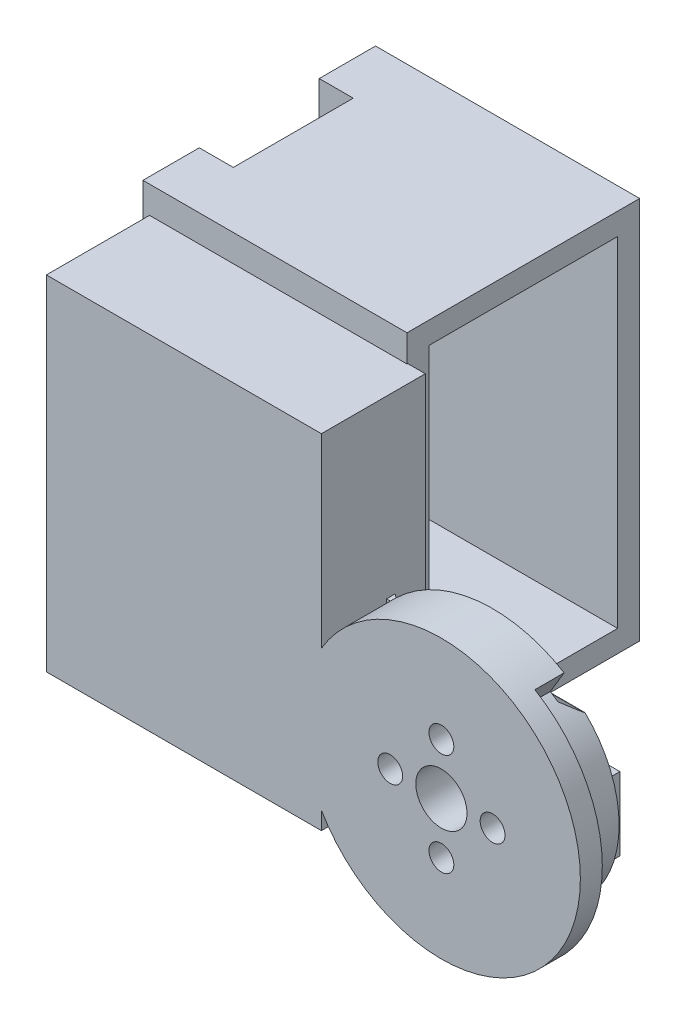
SolidWorks part; units mm, degrees
ref_plane "Front Plane" through (0, 0, 0) normal (0, 0, 1) x (1, 0, 0)
ref_plane "Top Plane" through (0, 0, 0) normal (0, 1, 0) x (1, 0, 0)
ref_plane "Right Plane" through (0, 0, 0) normal (1, 0, 0) x (0, 0, -1)
ref_plane "PZ_p23_000" through (0, 0, 23) normal (0, 0, 1) x (1, 0, 0)
sketch "S_cyl1" plane through (0, 0, 23) normal (0, 0, 1) x (1, 0, 0)
  circle A0 centre (0, 0) radius 19
  dimension "D1_S_cyl1" = 38
extrude "Boss_1" add sketch "S_cyl1" along normal blind 7
ref_plane "PZ_p21_000" through (0, 0, 21) normal (0, 0, 1) x (1, 0, 0)
sketch "S_prism2" plane through (0, 0, 21) normal (0, 0, 1) x (1, 0, 0)
  line L0 (-15.4919, 11) -> (15.4919, 11)
  line L1 (15.4919, -11) -> (-15.4919, -11)
  arc A0 (15.4919, 11) -> (15.4919, -11) centre (0, 0) cw
  arc A1 (-15.4919, -11) -> (-15.4919, 11) centre (0, 0) cw
extrude "Boss_2" add sketch "S_prism2" along normal blind 2.1
ref_plane "PZ_p19_600" through (0, 0, 19.6) normal (0, 0, 1) x (1, 0, 0)
sketch "S_box3" plane through (0, 0, 19.6) normal (0, 0, 1) x (1, 0, 0)
  line L0 (-14.2, -5) -> (14, -5)
  line L1 (14, -5) -> (14, 5)
  line L2 (14, 5) -> (-14.2, 5)
  line L3 (-14.2, 5) -> (-14.2, -5)
  dimension "P1" = 14.2
  dimension "P2" = 5
  dimension "P3" = 14
  dimension "P4" = 5
  dimension "P5" = 14
  dimension "P6" = 5
  dimension "P7" = 14.2
  dimension "P8" = 5
extrude "Boss_3" add sketch "S_box3" along normal blind 1.5
ref_plane "PZ_p15_800" through (0, 0, 15.8) normal (0, 0, 1) x (1, 0, 0)
sketch "S_box4" plane through (0, 0, 15.8) normal (0, 0, 1) x (1, 0, 0)
  line L0 (-54, -12) -> (-16.4, -12)
  line L1 (-16.4, -12) -> (-16.4, 35)
  line L2 (-16.4, 35) -> (-54, 35)
  line L3 (-54, 35) -> (-54, -12)
  dimension "P1" = 54
  dimension "P2" = 12
  dimension "P3" = 16.4
  dimension "P4" = 12
  dimension "P5" = 16.4
  dimension "P6" = 35
  dimension "P7" = 54
  dimension "P8" = 35
extrude "Boss_4" add sketch "S_box4" along normal blind 14.2
ref_plane "PX_m11_500" through (-11.5, 0, 0) normal (1, 0, 0) x (0, 0, -1)
sketch "S_prism5" plane through (-11.5, 0, 0) normal (1, 0, 0) x (0, 0, -1)
  line L0 (-21.05, 11) -> (-21.05, -12)
  line L1 (-21.05, -12) -> (-23.1, -15)
  line L2 (-23.1, -15) -> (-23.1, 12.5)
  line L3 (-23.1, 12.5) -> (-21.05, 11)
extrude "Boss_5" add sketch "S_prism5" along normal blind 23
ref_plane "PY_m11_000" through (0, -11, 0) normal (0, 1, 0) x (1, 0, 0)
sketch "S_prism6" plane through (0, -11, 0) normal (0, 1, 0) x (1, 0, 0)
  line L0 (-16.45, -21.1) -> (-16.45, -19.9)
  line L1 (-16.45, -19.9) -> (-14.8, -21.1)
  line L2 (-14.8, -21.1) -> (-16.45, -21.1)
extrude "Boss_6" add sketch "S_prism6" along normal blind 22
ref_plane "PZ_m15_900" through (0, 0, -15.9) normal (0, 0, 1) x (1, 0, 0)
sketch "S_box7" plane through (0, 0, -15.9) normal (0, 0, 1) x (1, 0, 0)
  line L0 (-54.9, 35.7) -> (-18.8, 35.7)
  line L1 (-18.8, 35.7) -> (-18.8, 38.7)
  line L2 (-18.8, 38.7) -> (-54.9, 38.7)
  line L3 (-54.9, 38.7) -> (-54.9, 35.7)
  dimension "P1" = 54.9
  dimension "P2" = 35.7
  dimension "P3" = 18.8
  dimension "P4" = 35.7
  dimension "P5" = 18.8
  dimension "P6" = 38.7
  dimension "P7" = 54.9
  dimension "P8" = 38.7
extrude "Boss_7" add sketch "S_box7" along normal blind 31.8
sketch "S_box8" plane through (0, 0, -15.9) normal (0, 0, 1) x (1, 0, 0)
  line L0 (-54.9, -13.7) -> (-18.8, -13.7)
  line L1 (-18.8, -13.7) -> (-18.8, -10.7)
  line L2 (-18.8, -10.7) -> (-54.9, -10.7)
  line L3 (-54.9, -10.7) -> (-54.9, -13.7)
  dimension "P1" = 54.9
  dimension "P2" = 13.7
  dimension "P3" = 18.8
  dimension "P4" = 13.7
  dimension "P5" = 18.8
  dimension "P6" = 10.7
  dimension "P7" = 54.9
  dimension "P8" = 10.7
extrude "Boss_8" add sketch "S_box8" along normal blind 31.8
sketch "S_box9" plane through (0, 0, -15.9) normal (0, 0, 1) x (1, 0, 0)
  line L0 (-54.9, -13.7) -> (-18.8, -13.7)
  line L1 (-18.8, -13.7) -> (-18.8, 38.7)
  line L2 (-18.8, 38.7) -> (-54.9, 38.7)
  line L3 (-54.9, 38.7) -> (-54.9, -13.7)
  dimension "P1" = 54.9
  dimension "P2" = 13.7
  dimension "P3" = 18.8
  dimension "P4" = 13.7
  dimension "P5" = 18.8
  dimension "P6" = 38.7
  dimension "P7" = 54.9
  dimension "P8" = 38.7
extrude "Boss_9" add sketch "S_box9" along normal blind 3
ref_plane "PZ_p12_900" through (0, 0, 12.9) normal (0, 0, 1) x (1, 0, 0)
sketch "S_box10" plane through (0, 0, 12.9) normal (0, 0, 1) x (1, 0, 0)
  line L0 (-54.9, -13.7) -> (-18.8, -13.7)
  line L1 (-18.8, -13.7) -> (-18.8, 38.7)
  line L2 (-18.8, 38.7) -> (-54.9, 38.7)
  line L3 (-54.9, 38.7) -> (-54.9, -13.7)
  dimension "P1" = 54.9
  dimension "P2" = 13.7
  dimension "P3" = 18.8
  dimension "P4" = 13.7
  dimension "P5" = 18.8
  dimension "P6" = 38.7
  dimension "P7" = 54.9
  dimension "P8" = 38.7
extrude "Boss_10" add sketch "S_box10" along normal blind 3
sketch "S_box11" plane through (0, 0, -15.9) normal (0, 0, 1) x (1, 0, 0)
  line L0 (-54.9, -13.7) -> (-50.3, -13.7)
  line L1 (-50.3, -13.7) -> (-50.3, 38.7)
  line L2 (-50.3, 38.7) -> (-54.9, 38.7)
  line L3 (-54.9, 38.7) -> (-54.9, -13.7)
  dimension "P1" = 54.9
  dimension "P2" = 13.7
  dimension "P3" = 50.3
  dimension "P4" = 13.7
  dimension "P5" = 50.3
  dimension "P6" = 38.7
  dimension "P7" = 54.9
  dimension "P8" = 38.7
extrude "Boss_11" add sketch "S_box11" along normal blind 31.8
ref_plane "PX_m55_000" through (-55, 0, 0) normal (1, 0, 0) x (0, 0, -1)
sketch "S_hole12" plane through (-55, 0, 0) normal (1, 0, 0) x (0, 0, -1)
  circle A0 centre (0, 0) radius 10.5
  dimension "D1_S_hole12" = 21
extrude "Hole_12" cut sketch "S_hole12" along normal blind 4.8
ref_plane "PZ_m9_700" through (0, 0, -9.7) normal (0, 0, 1) x (1, 0, 0)
sketch "S_cut13" plane through (0, 0, -9.7) normal (0, 0, 1) x (1, 0, 0)
  line L0 (-55, 10.9) -> (-50.25, 10.9)
  line L1 (-50.25, 10.9) -> (-50.25, 30.4)
  line L2 (-50.25, 30.4) -> (-55, 30.4)
  line L3 (-55, 30.4) -> (-55, 10.9)
  dimension "P1" = 55
  dimension "P2" = 10.9
  dimension "P3" = 50.25
  dimension "P4" = 10.9
  dimension "P5" = 50.25
  dimension "P6" = 30.4
  dimension "P7" = 55
  dimension "P8" = 30.4
extrude "Pocket_13" cut sketch "S_cut13" along normal blind 19.4
ref_plane "PZ_m8_200" through (0, 0, -8.2) normal (0, 0, 1) x (1, 0, 0)
sketch "S_cut14" plane through (0, 0, -8.2) normal (0, 0, 1) x (1, 0, 0)
  line L0 (-55, 30.4) -> (-50.25, 30.4)
  line L1 (-50.25, 30.4) -> (-50.25, 39.2)
  line L2 (-50.25, 39.2) -> (-55, 39.2)
  line L3 (-55, 39.2) -> (-55, 30.4)
  dimension "P1" = 55
  dimension "P2" = 30.4
  dimension "P3" = 50.25
  dimension "P4" = 30.4
  dimension "P5" = 50.25
  dimension "P6" = 39.2
  dimension "P7" = 55
  dimension "P8" = 39.2
extrude "Pocket_14" cut sketch "S_cut14" along normal blind 16.4
ref_plane "PZ_m3_500" through (0, 0, -3.5) normal (0, 0, 1) x (1, 0, 0)
sketch "S_cut15" plane through (0, 0, -3.5) normal (0, 0, 1) x (1, 0, 0)
  line L0 (-55, 0) -> (-50.25, 0)
  line L1 (-50.25, 0) -> (-50.25, 11)
  line L2 (-50.25, 11) -> (-55, 11)
  line L3 (-55, 11) -> (-55, 0)
  dimension "P1" = 55
  dimension "P2" = 50.25
  dimension "P3" = 50.25
  dimension "P4" = 11
  dimension "P5" = 55
  dimension "P6" = 11
extrude "Pocket_15" cut sketch "S_cut15" along normal blind 7
ref_plane "PZ_m16_400" through (0, 0, -16.4) normal (0, 0, 1) x (1, 0, 0)
sketch "S_cut16" plane through (0, 0, -16.4) normal (0, 0, 1) x (1, 0, 0)
  line L0 (-55.1, -10) -> (-52.2, -10)
  line L1 (-52.2, -10) -> (-52.2, 10)
  line L2 (-52.2, 10) -> (-55.1, 10)
  line L3 (-55.1, 10) -> (-55.1, -10)
  dimension "P1" = 55.1
  dimension "P2" = 10
  dimension "P3" = 52.2
  dimension "P4" = 10
  dimension "P5" = 52.2
  dimension "P6" = 10
  dimension "P7" = 55.1
  dimension "P8" = 10
extrude "Pocket_16" cut sketch "S_cut16" along normal blind 16.4
sketch "S_hole17" plane through (-55, 0, 0) normal (1, 0, 0) x (0, 0, -1)
  circle A0 centre (-10.25, 8.3) radius 1.1
  dimension "D1_S_hole17" = 2.2
  dimension "P2" = 10.25
  dimension "P3" = 8.3
extrude "Hole_17" cut sketch "S_hole17" along normal blind 4.8
sketch "S_hole18" plane through (-55, 0, 0) normal (1, 0, 0) x (0, 0, -1)
  circle A0 centre (-10.25, 8.3) radius 2.3
  dimension "D1_S_hole18" = 4.6
  dimension "P2" = 10.25
  dimension "P3" = 8.3
extrude "Hole_18" cut sketch "S_hole18" along normal blind 1.7
sketch "S_hole19" plane through (-55, 0, 0) normal (1, 0, 0) x (0, 0, -1)
  circle A0 centre (10.25, 32.75) radius 1.1
  dimension "D1_S_hole19" = 2.2
  dimension "P2" = 10.25
  dimension "P3" = 32.75
extrude "Hole_19" cut sketch "S_hole19" along normal blind 4.8
sketch "S_hole20" plane through (-55, 0, 0) normal (1, 0, 0) x (0, 0, -1)
  circle A0 centre (10.25, 32.75) radius 2.3
  dimension "D1_S_hole20" = 4.6
  dimension "P2" = 10.25
  dimension "P3" = 32.75
extrude "Hole_20" cut sketch "S_hole20" along normal blind 1.7
sketch "S_hole21" plane through (-55, 0, 0) normal (1, 0, 0) x (0, 0, -1)
  circle A0 centre (-10.25, 32.75) radius 1.1
  dimension "D1_S_hole21" = 2.2
  dimension "P2" = 10.25
  dimension "P3" = 32.75
extrude "Hole_21" cut sketch "S_hole21" along normal blind 4.8
sketch "S_hole22" plane through (-55, 0, 0) normal (1, 0, 0) x (0, 0, -1)
  circle A0 centre (-10.25, 32.75) radius 2.3
  dimension "D1_S_hole22" = 4.6
  dimension "P2" = 10.25
  dimension "P3" = 32.75
extrude "Hole_22" cut sketch "S_hole22" along normal blind 1.7
ref_plane "PZ_p20_900" through (0, 0, 20.9) normal (0, 0, 1) x (1, 0, 0)
sketch "S_pcut23" plane through (0, 0, 20.9) normal (0, 0, 1) x (1, 0, 0)
  line L0 (-14.7923, -12.8588) -> (-11.5471, -10.0377)
  line L1 (7.8801, 13.1147) -> (10.0947, 16.8005)
  arc A0 (10.0947, 16.8005) -> (-14.7923, -12.8588) centre (0, 0) cw
  arc A1 (-11.5471, -10.0377) -> (7.8801, 13.1147) centre (0, 0) ccw
extrude "Cut_23" cut sketch "S_pcut23" along normal blind 6.1
ref_plane "PZ_p19_500" through (0, 0, 19.5) normal (0, 0, 1) x (1, 0, 0)
sketch "S_hole24" plane through (0, 0, 19.5) normal (0, 0, 1) x (1, 0, 0)
  circle A0 centre (0, 0) radius 3.5
  dimension "D1_S_hole24" = 7
extrude "Hole_24" cut sketch "S_hole24" along normal blind 10.6
sketch "S_hole25" plane through (0, 0, 19.5) normal (0, 0, 1) x (1, 0, 0)
  circle A0 centre (7, 0) radius 1.7
  dimension "D1_S_hole25" = 3.4
  dimension "P2" = 7
extrude "Hole_25" cut sketch "S_hole25" along normal blind 10.6
sketch "S_hole26" plane through (0, 0, 19.5) normal (0, 0, 1) x (1, 0, 0)
  circle A0 centre (0, -7) radius 1.7
  dimension "D1_S_hole26" = 3.4
  dimension "P2" = 7
extrude "Hole_26" cut sketch "S_hole26" along normal blind 10.6
sketch "S_hole27" plane through (0, 0, 19.5) normal (0, 0, 1) x (1, 0, 0)
  circle A0 centre (-7, 0) radius 1.7
  dimension "D1_S_hole27" = 3.4
  dimension "P2" = 7
extrude "Hole_27" cut sketch "S_hole27" along normal blind 10.6
sketch "S_hole28" plane through (0, 0, 19.5) normal (0, 0, 1) x (1, 0, 0)
  circle A0 centre (0, 7) radius 1.7
  dimension "D1_S_hole28" = 3.4
  dimension "P2" = 7
extrude "Hole_28" cut sketch "S_hole28" along normal blind 10.6
ref_plane "PZ_p19_400" through (0, 0, 19.4) normal (0, 0, 1) x (1, 0, 0)
sketch "S_hole29" plane through (0, 0, 19.4) normal (0, 0, 1) x (1, 0, 0)
  circle A0 centre (7, 0) radius 3.2
  dimension "D1_S_hole29" = 6.4
  dimension "P2" = 7
extrude "Hole_29" cut sketch "S_hole29" along normal blind 7.6
sketch "S_hole30" plane through (0, 0, 19.4) normal (0, 0, 1) x (1, 0, 0)
  circle A0 centre (0, -7) radius 3.2
  dimension "D1_S_hole30" = 6.4
  dimension "P2" = 7
extrude "Hole_30" cut sketch "S_hole30" along normal blind 7.6
sketch "S_hole31" plane through (0, 0, 19.4) normal (0, 0, 1) x (1, 0, 0)
  circle A0 centre (-7, 0) radius 3.2
  dimension "D1_S_hole31" = 6.4
  dimension "P2" = 7
extrude "Hole_31" cut sketch "S_hole31" along normal blind 7.6
sketch "S_hole32" plane through (0, 0, 19.4) normal (0, 0, 1) x (1, 0, 0)
  circle A0 centre (0, 7) radius 3.2
  dimension "D1_S_hole32" = 6.4
  dimension "P2" = 7
extrude "Hole_32" cut sketch "S_hole32" along normal blind 7.6
equation "\"plate_t\" = 3"
equation "\"clearance\" = 0.5"
